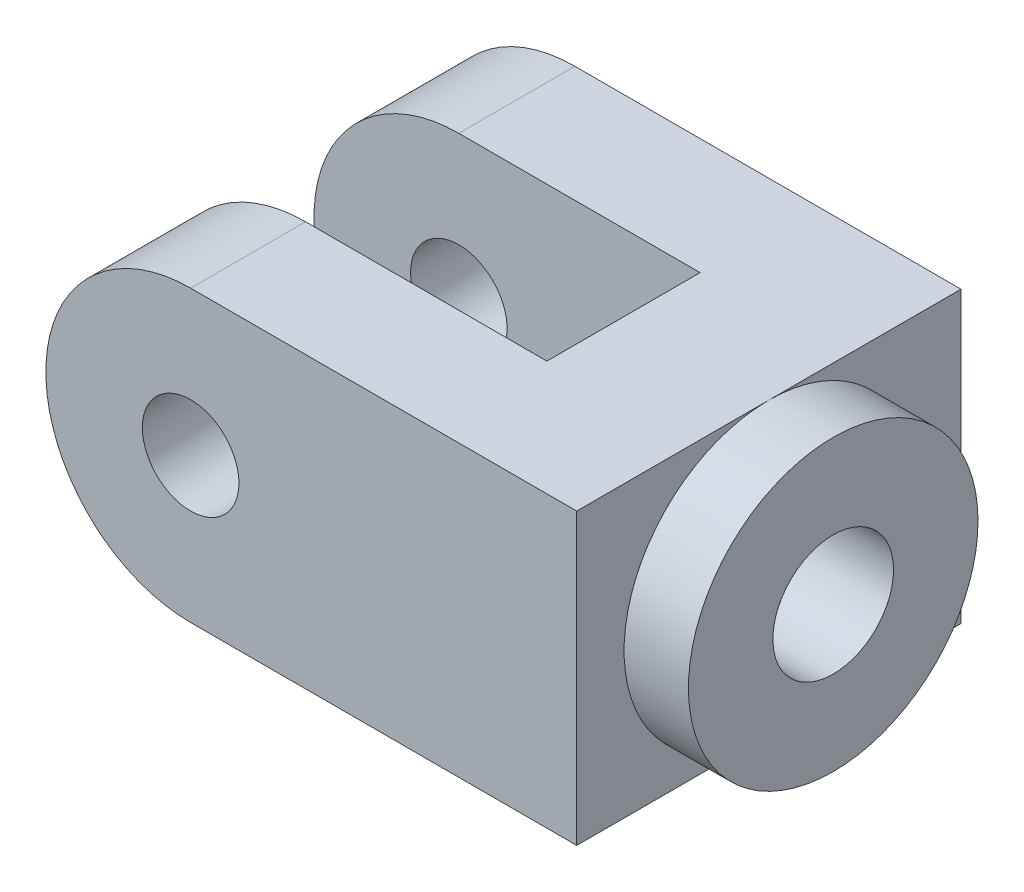
SolidWorks part; units mm, degrees
ref_plane "Front Plane" through (0, 0, 0) normal (0, 0, 1) x (1, 0, 0)
ref_plane "Top Plane" through (0, 0, 0) normal (0, 1, 0) x (1, 0, 0)
ref_plane "Right Plane" through (0, 0, 0) normal (1, 0, 0) x (0, 0, -1)
sketch "Sketch1" plane through (0, 0, 0) normal (0, 0, 1) x (1, 0, 0)
  line L1 (-66, 36) -> (66, 36)
  line L2 (-66, 36) -> (-66, -36)
  line L3 (-66, -36) -> (66, -36)
  line L4 (66, 36) -> (66, -36)
  line L5 (-66, 36) -> (66, -36) construction
  line L6 (-66, -36) -> (66, 36) construction
  point P0 (0, 0)
  dimension "D1" = 132
  dimension "D2" = 72
extrude "Boss-Extrude1" add sketch "Sketch1" along normal blind 95.55
sketch "Sketch2" plane through (0, 0, 95.55) normal (0, 0, 1) x (1, 0, 0)
  line L0 (66, 36) -> (-66, 36) construction
  line L1 (-66, -36) -> (66, -36) construction
  line L2 (-66, 36) -> (-66, -36) construction
  arc A0 (-30, 36) -> (-30, -36) centre (-30, 0) ccw
  dimension "D1" = 36
extrude "Cut-Extrude3" cut sketch "Sketch2" against normal through all and the other way through all flip side to cut
sketch "Sketch3" plane through (0, 36, 0) normal (0, 1, 0) x (1, 0, 0)
  line L0 (-66, 0) -> (-66, -95.55) construction
  line L1 (30, -28.87) -> (-66, -28.87)
  line L2 (30, -28.87) -> (30, -66.97)
  line L3 (30, -66.97) -> (-66, -66.97)
  line L4 (-66, -28.87) -> (-66, -66.97)
  point P6 (0, 0)
  dimension "D1" = 38.1
  dimension "D2" = 60
  dimension "D3" = 28.58
extrude "Cut-Extrude4" cut sketch "Sketch3" against normal through all
sketch "Sketch4" plane through (66, 0, 0) normal (1, 0, 0) x (0, 0, -1)
  circle A0 centre (-47.775, 0) radius 15
  dimension "D1" = 30
extrude "Cut-Extrude5" cut sketch "Sketch4" against normal through all
sketch "Sketch5" plane through (66, 0, 0) normal (1, 0, 0) x (0, 0, -1)
  circle A0 centre (-47.775, 0) radius 36
  circle A1 centre (-47.775, 0) radius 15 construction
  circle A2 centre (-47.775, 0) radius 15
  dimension "D1" = 72
extrude "Boss-Extrude2" add sketch "Sketch5" along normal blind 16
sketch "Sketch6" plane through (0, 0, 0) normal (0, 0, -1) x (-1, 0, 0)
  circle A0 centre (30, 0) radius 12
  dimension "D1" = 24
extrude "Cut-Extrude6" cut sketch "Sketch6" against normal through all
